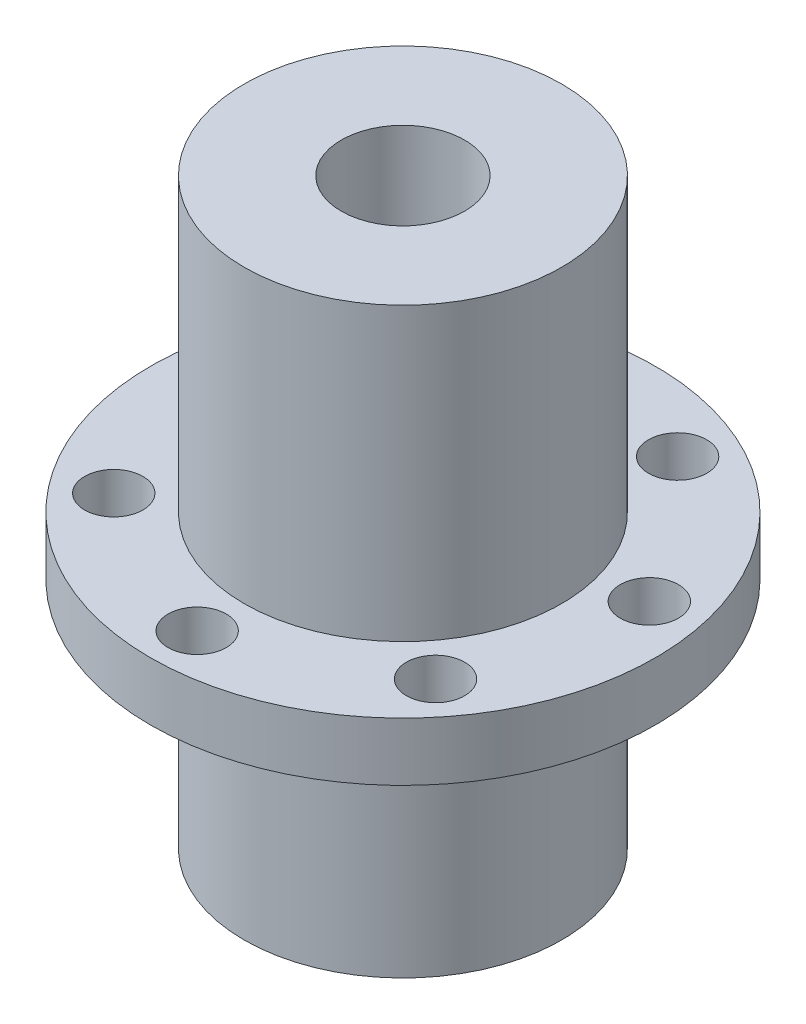
SolidWorks part; units mm, degrees
ref_plane "Front Plane" through (0, 0, 0) normal (0, 0, 1) x (1, 0, 0)
ref_plane "Top Plane" through (0, 0, 0) normal (0, 1, 0) x (1, 0, 0)
ref_plane "Right Plane" through (0, 0, 0) normal (1, 0, 0) x (0, 0, -1)
sketch "Sketch1" plane through (0, 0, 0) normal (0, 1, 0) x (1, 0, 0)
  circle A0 centre (0, 0) radius 3.175
  circle A1 centre (0, 0) radius 8.175
  circle A2 centre (0, 0) radius 13
  point P25 (0, 0)
extrude "Boss-Extrude1" add sketch "Sketch1" along normal blind 15 and the other way blind 15 contours A1 A0 region at (-7.9438, 0, 0)
extrude "Boss-Extrude2" add sketch "Sketch1<3>" against normal blind 3 separate body contours A2 A1 region at (-12.6323, 0, 0)
sketch "Sketch1<3>" plane through (0, 0, 0) normal (0, 1, 0) x (1, 0, 0) same geometry as "Sketch1"
sketch "Sketch2" plane through (0, 0, 0) normal (1, 0, 0) x (0, 0, -1)
  circle A0 centre (0, 6.7029) radius 2.5
  point P2 (0, 6.3265)
  point P3 (0, 6.7029)
extrude "Cut-Extrude1" cut sketch "Sketch2" against normal blind 11
sketch "Sketch3" plane through (0, -15, 0) normal (0, -1, 0) x (1, 0, 0)
  circle A1 centre (0, 10.5946) radius 1.5
  circle A2 centre (8.2832, 6.6056) radius 1.5
  circle A3 centre (10.329, -2.3575) radius 1.5
  circle A4 centre (4.5968, -9.5454) radius 1.5
  circle A5 centre (-4.5968, -9.5454) radius 1.5
  circle A6 centre (-10.329, -2.3575) radius 1.5
  circle A7 centre (-8.2832, 6.6056) radius 1.5
  point P14 (0, 0)
  dimension "D1" = 7
extrude "Cut-Extrude2" cut sketch "Sketch3" against normal through all and the other way through all
